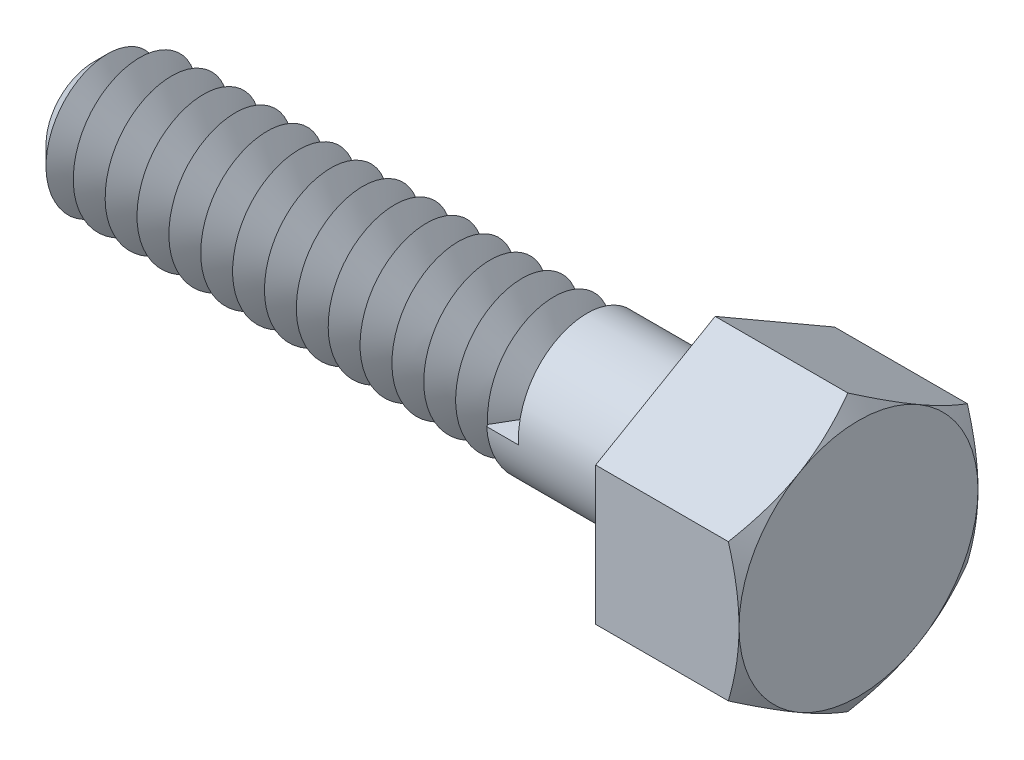
SolidWorks part; units mm, degrees
ref_plane "Front Plane" through (0, 0, 0) normal (0, 0, 1) x (1, 0, 0)
ref_plane "Top Plane" through (0, 0, 0) normal (0, 1, 0) x (1, 0, 0)
ref_plane "Right Plane" through (0, 0, 0) normal (1, 0, 0) x (0, 0, -1)
sketch "Sketch2" plane through (0, 0, 0) normal (1, 0, 0) x (0, 0, -1)
  line L1 (0, -2.8868) -> (2.5, -1.4434)
  line L2 (2.5, -1.4434) -> (2.5, 1.4434)
  line L3 (2.5, 1.4434) -> (0, 2.8868)
  line L4 (0, 2.8868) -> (-2.5, 1.4434)
  line L5 (-2.5, 1.4434) -> (-2.5, -1.4434)
  line L6 (-2.5, -1.4434) -> (0, -2.8868)
  circle A0 centre (0, 0) radius 2.5 construction
  dimension "D1" = 5
extrude "Boss-Extrude1" add sketch "Sketch2" along normal blind 3
sketch "Sketch3" plane through (3, 0, 0) normal (1, 0, 0) x (0, 0, -1)
  circle A0 centre (0, 0) radius 2.5
extrude "Cut-Extrude1" cut sketch "Sketch3" against normal blind 3 draft 60 flip side to cut
sketch "Sketch4" plane through (0, 0, 0) normal (-1, 0, 0) x (0, 0, 1)
  circle A0 centre (0, 0) radius 1.5
extrude "Boss-Extrude2" add sketch "Sketch4" along normal blind 13
chamfer "Chamfer1" distance 0.5 angle 45 1 edges at (-13, 0, 1.5)
sketch "Sketch5" plane through (-13, 0, 0) normal (-1, 0, 0) x (0, 0, 1)
  circle A0 centre (0, 0) radius 1.5
curve "Helix/Spiral1" pitch 0.6667 height 10 turns 15
sketch "Sketch6" plane through (0, 0, 0) normal (0, 1, 0) x (1, 0, 0)
  line L1 (-12.9702, -0.8743) -> (-13.4744, -1.7379)
  line L2 (-13.4744, -1.7379) -> (-12.4744, -1.7427)
  line L3 (-12.4744, -1.7427) -> (-12.9702, -0.8743)
  circle A0 centre (-12.973, -1.4516) radius 0.2887 construction
  spline S0 degree 3 poles (-13, -1.5) (-12.9862, -1.5) (-12.9583, -1.4219) (-12.9167, -1.0883) (-12.875, -0.589) (-12.8333, 0) (-12.7917, 0.589) (-12.75, 1.0883) (-12.7083, 1.4219) (-12.6667, 1.5391) (-12.625, 1.4219) (-12.5833, 1.0883) (-12.5417, 0.589) (-12.5, 0) (-12.4583, -0.589) (-12.4167, -1.0883) (-12.375, -1.4219) (-12.3333, -1.5391) (-12.2917, -1.4219) (-12.25, -1.0883) (-12.2083, -0.589) (-12.1667, 0) (-12.125, 0.589) (-12.0833, 1.0883) (-12.0417, 1.4219) (-12, 1.5391) (-11.9583, 1.4219) (-11.9167, 1.0883) (-11.875, 0.589) (-11.8333, 0) (-11.7917, -0.589) (-11.75, -1.0883) (-11.7083, -1.4219) (-11.6667, -1.5391) (-11.625, -1.4219) (-11.5833, -1.0883) (-11.5417, -0.589) (-11.5, 0) (-11.4583, 0.589) (-11.4167, 1.0883) (-11.375, 1.4219) (-11.3333, 1.5391) (-11.2917, 1.4219) (-11.25, 1.0883) (-11.2083, 0.589) (-11.1667, 0) (-11.125, -0.589) (-11.0833, -1.0883) (-11.0417, -1.4219) (-11, -1.5391) (-10.9583, -1.4219) (-10.9167, -1.0883) (-10.875, -0.589) (-10.8333, 0) (-10.7917, 0.589) (-10.75, 1.0883) (-10.7083, 1.4219) (-10.6667, 1.5391) (-10.625, 1.4219) (-10.5833, 1.0883) (-10.5417, 0.589) (-10.5, 0) (-10.4583, -0.589) (-10.4167, -1.0883) (-10.375, -1.4219) (-10.3333, -1.5391) (-10.2917, -1.4219) (-10.25, -1.0883) (-10.2083, -0.589) (-10.1667, 0) (-10.125, 0.589) (-10.0833, 1.0883) (-10.0417, 1.4219) (-10, 1.5391) (-9.9583, 1.4219) (-9.9167, 1.0883) (-9.875, 0.589) (-9.8333, 0) (-9.7917, -0.589) (-9.75, -1.0883) (-9.7083, -1.4219) (-9.6667, -1.5391) (-9.625, -1.4219) (-9.5833, -1.0883) (-9.5417, -0.589) (-9.5, 0) (-9.4583, 0.589) (-9.4167, 1.0883) (-9.375, 1.4219) (-9.3333, 1.5391) (-9.2917, 1.4219) (-9.25, 1.0883) (-9.2083, 0.589) (-9.1667, 0) (-9.125, -0.589) (-9.0833, -1.0883) (-9.0417, -1.4219) (-9, -1.5391) (-8.9583, -1.4219) (-8.9167, -1.0883) (-8.875, -0.589) (-8.8333, 0) (-8.7917, 0.589) (-8.75, 1.0883) (-8.7083, 1.4219) (-8.6667, 1.5391) (-8.625, 1.4219) (-8.5833, 1.0883) (-8.5417, 0.589) (-8.5, 0) (-8.4583, -0.589) (-8.4167, -1.0883) (-8.375, -1.4219) (-8.3333, -1.5391) (-8.2917, -1.4219) (-8.25, -1.0883) (-8.2083, -0.589) (-8.1667, 0) (-8.125, 0.589) (-8.0833, 1.0883) (-8.0417, 1.4219) (-8, 1.5391) (-7.9583, 1.4219) (-7.9167, 1.0883) (-7.875, 0.589) (-7.8333, 0) (-7.7917, -0.589) (-7.75, -1.0883) (-7.7083, -1.4219) (-7.6667, -1.5391) (-7.625, -1.4219) (-7.5833, -1.0883) (-7.5417, -0.589) (-7.5, 0) (-7.4583, 0.589) (-7.4167, 1.0883) (-7.375, 1.4219) (-7.3333, 1.5391) (-7.2917, 1.4219) (-7.25, 1.0883) (-7.2083, 0.589) (-7.1667, 0) (-7.125, -0.589) (-7.0833, -1.0883) (-7.0417, -1.4219) (-7, -1.5391) (-6.9583, -1.4219) (-6.9167, -1.0883) (-6.875, -0.589) (-6.8333, 0) (-6.7917, 0.589) (-6.75, 1.0883) (-6.7083, 1.4219) (-6.6667, 1.5391) (-6.625, 1.4219) (-6.5833, 1.0883) (-6.5417, 0.589) (-6.5, 0) (-6.4583, -0.589) (-6.4167, -1.0883) (-6.375, -1.4219) (-6.3333, -1.5391) (-6.2917, -1.4219) (-6.25, -1.0883) (-6.2083, -0.589) (-6.1667, 0) (-6.125, 0.589) (-6.0833, 1.0883) (-6.0417, 1.4219) (-6, 1.5391) (-5.9583, 1.4219) (-5.9167, 1.0883) (-5.875, 0.589) (-5.8333, 0) (-5.7917, -0.589) (-5.75, -1.0883) (-5.7083, -1.4219) (-5.6667, -1.5391) (-5.625, -1.4219) (-5.5833, -1.0883) (-5.5417, -0.589) (-5.5, 0) (-5.4583, 0.589) (-5.4167, 1.0883) (-5.375, 1.4219) (-5.3333, 1.5391) (-5.2917, 1.4219) (-5.25, 1.0883) (-5.2083, 0.589) (-5.1667, 0) (-5.125, -0.589) (-5.0833, -1.0883) (-5.0417, -1.4219) (-5, -1.5391) (-4.9583, -1.4219) (-4.9167, -1.0883) (-4.875, -0.589) (-4.8333, 0) (-4.7917, 0.589) (-4.75, 1.0883) (-4.7083, 1.4219) (-4.6667, 1.5391) (-4.625, 1.4219) (-4.5833, 1.0883) (-4.5417, 0.589) (-4.5, 0) (-4.4583, -0.589) (-4.4167, -1.0883) (-4.375, -1.4219) (-4.3333, -1.5391) (-4.2917, -1.4219) (-4.25, -1.0883) (-4.2083, -0.589) (-4.1667, 0) (-4.125, 0.589) (-4.0833, 1.0883) (-4.0417, 1.4219) (-4, 1.5391) (-3.9583, 1.4219) (-3.9167, 1.0883) (-3.875, 0.589) (-3.8333, 0) (-3.7917, -0.589) (-3.75, -1.0883) (-3.7083, -1.4219) (-3.6667, -1.5391) (-3.625, -1.4219) (-3.5833, -1.0883) (-3.5417, -0.589) (-3.5, 0) (-3.4583, 0.589) (-3.4167, 1.0883) (-3.375, 1.4219) (-3.3333, 1.5391) (-3.2917, 1.4219) (-3.25, 1.0883) (-3.2083, 0.589) (-3.1667, 0) (-3.125, -0.589) (-3.0833, -1.0883) (-3.0417, -1.4219) (-3.0138, -1.5) (-3, -1.5) knots 0 0 0 0 0.004167 0.008333 0.0125 0.016667 0.020833 0.025 0.029167 0.033333 0.0375 0.041667 0.045833 0.05 0.054167 0.058333 0.0625 0.066667 0.070833 0.075 0.079167 0.083333 0.0875 0.091667 0.095833 0.1 0.104167 0.108333 0.1125 0.116667 0.120833 0.125 0.129167 0.133333 0.1375 0.141667 0.145833 0.15 0.154167 0.158333 0.1625 0.166667 0.170833 0.175 0.179167 0.183333 0.1875 0.191667 0.195833 0.2 0.204167 0.208333 0.2125 0.216667 0.220833 0.225 0.229167 0.233333 0.2375 0.241667 0.245833 0.25 0.254167 0.258333 0.2625 0.266667 0.270833 0.275 0.279167 0.283333 0.2875 0.291667 0.295833 0.3 0.304167 0.308333 0.3125 0.316667 0.320833 0.325 0.329167 0.333333 0.3375 0.341667 0.345833 0.35 0.354167 0.358333 0.3625 0.366667 0.370833 0.375 0.379167 0.383333 0.3875 0.391667 0.395833 0.4 0.404167 0.408333 0.4125 0.416667 0.420833 0.425 0.429167 0.433333 0.4375 0.441667 0.445833 0.45 0.454167 0.458333 0.4625 0.466667 0.470833 0.475 0.479167 0.483333 0.4875 0.491667 0.495833 0.5 0.504167 0.508333 0.5125 0.516667 0.520833 0.525 0.529167 0.533333 0.5375 0.541667 0.545833 0.55 0.554167 0.558333 0.5625 0.566667 0.570833 0.575 0.579167 0.583333 0.5875 0.591667 0.595833 0.6 0.604167 0.608333 0.6125 0.616667 0.620833 0.625 0.629167 0.633333 0.6375 0.641667 0.645833 0.65 0.654167 0.658333 0.6625 0.666667 0.670833 0.675 0.679167 0.683333 0.6875 0.691667 0.695833 0.7 0.704167 0.708333 0.7125 0.716667 0.720833 0.725 0.729167 0.733333 0.7375 0.741667 0.745833 0.75 0.754167 0.758333 0.7625 0.766667 0.770833 0.775 0.779167 0.783333 0.7875 0.791667 0.795833 0.8 0.804167 0.808333 0.8125 0.816667 0.820833 0.825 0.829167 0.833333 0.8375 0.841667 0.845833 0.85 0.854167 0.858333 0.8625 0.866667 0.870833 0.875 0.879167 0.883333 0.8875 0.891667 0.895833 0.9 0.904167 0.908333 0.9125 0.916667 0.920833 0.925 0.929167 0.933333 0.9375 0.941667 0.945833 0.95 0.954167 0.958333 0.9625 0.966667 0.970833 0.975 0.979167 0.983333 0.9875 0.991667 0.995833 1 1 1 1 construction
sweep "Cut-Sweep1" cut profiles "Sketch6" path "Helix/Spiral1"
